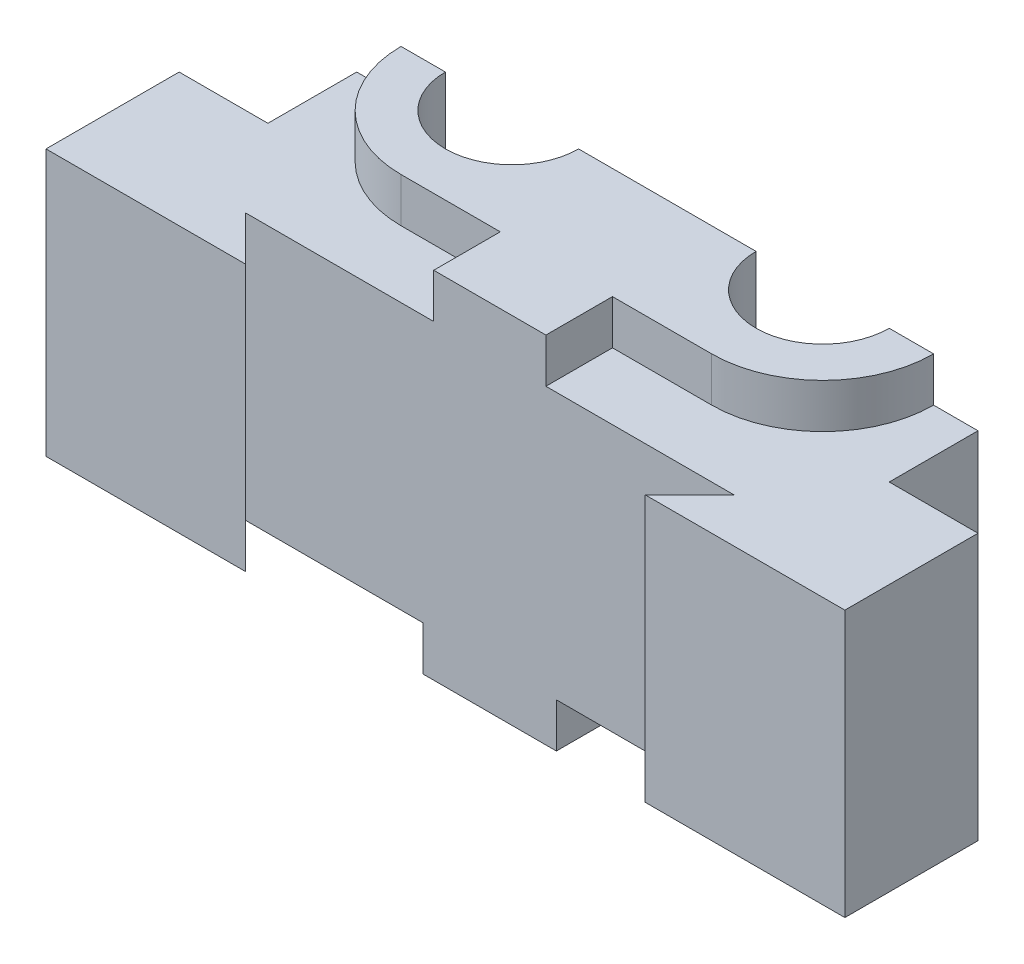
SolidWorks part; units mm, degrees
ref_plane "Front Plane" through (0, 0, 0) normal (0, 0, 1) x (1, 0, 0)
ref_plane "Top Plane" through (0, 0, 0) normal (0, 1, 0) x (1, 0, 0)
ref_plane "Right Plane" through (0, 0, 0) normal (1, 0, 0) x (0, 0, -1)
sketch "Sketch1" plane through (0, 0, 0) normal (0, 1, 0) x (1, 0, 0)
  line L0 (0, 59.4374) -> (0, -59.4374) construction
  line L1 (-91.3835, 0) -> (103.8781, 0) construction
  line L2 (-35, 0) -> (35, 0)
  line L3 (-35, 0) -> (-35, -10)
  line L4 (35, 0) -> (35, -10)
  line L5 (-45, -25) -> (-22.5, -25)
  line L6 (-45, -25) -> (-45, -10)
  line L7 (-45, -10) -> (-35, -10)
  line L8 (45, -10) -> (35, -10)
  line L9 (45, -25) -> (45, -10)
  line L10 (-27.5, -20) -> (27.5, -20)
  line L11 (-27.5, -20) -> (-22.5, -25)
  line L12 (27.5, -20) -> (22.5, -25)
  line L13 (22.5, -25) -> (45, -25)
  point P7 (0, 0)
  point P17 (0, -20)
  dimension "D1" = 70
  dimension "D2" = 10
  dimension "D3" = 15
  dimension "D4" = 90
  dimension "D5" = 55
  dimension "D6" = 5
  dimension "D7" = 45
  dimension "D8" = 22.5
extrude "Boss-Extrude1" add sketch "Sketch1" along normal blind 30
sketch "Sketch3" plane through (0, 30, 0) normal (0, 1, 0) x (1, 0, 0)
  line L0 (35, 0) -> (-35, 0) construction
  line L1 (0, 23.9193) -> (0, -33.7486) construction
  line L3 (-6.3201, -20) -> (6.3201, -20)
  line L4 (-27.5, -20) -> (27.5, -20) construction
  line L5 (-6.3201, -20) -> (-6.3201, -12.5)
  line L6 (-6.3201, -12.5) -> (-17.5, -12.5)
  line L7 (6.3201, -20) -> (6.3201, -12.5)
  line L8 (6.3201, -12.5) -> (17.5, -12.5)
  line L9 (-35, 0) -> (35, 0) construction
  line L10 (-30, 0) -> (30, 0)
  arc A0 (-25, 0) -> (-10, 0) centre (-17.5, 0) ccw
  arc A1 (10, 0) -> (25, 0) centre (17.5, 0) ccw
  arc A2 (-30, 0) -> (-17.5, -12.5) centre (-17.5, 0) ccw
  arc A3 (30, 0) -> (17.5, -12.5) centre (17.5, 0) cw
  point P15 (0, -20)
  line M15 (-27.5, -20) -> (27.5, -20)
  line M21 (35, 0) -> (-35, 0)
  dimension "D1" = 12.5
  dimension "D2" = 7.5
  dimension "D5" = 7.5
  dimension "D3" = 12.6403
  dimension "D4" = 17.5
extrude "Boss-Extrude2" add sketch "Sketch3" along normal blind 5 contours A3 A1 A0 A2 L6 L5 L7 L8 M21 M15 region at (0, 30, 8.3432)
sketch "Sketch5" plane through (0, 0, 0) normal (0, -1, 0) x (1, 0, 0)
  line L0 (0, 42.5009) -> (0, -21.0991) construction
  line L1 (-7.5, 20) -> (7.5, 20)
  line L2 (-27.5, 20) -> (27.5, 20) construction
  line L3 (35, 0) -> (-35, 0) construction
  line L4 (-30, 0) -> (30, 0) construction
  line L5 (-17.5, 12.5) -> (-7.5, 12.5)
  line L6 (-7.5, 12.5) -> (-7.5, 20)
  line L7 (7.5, 12.5) -> (7.5, 20)
  line L8 (17.5, 12.5) -> (7.5, 12.5)
  line L9 (-30, 0) -> (30, 0)
  arc A0 (-17.5, 12.5) -> (-30, 0) centre (-17.5, 0) ccw
  arc A1 (-10, 0) -> (-25, 0) centre (-17.5, 0) ccw
  arc A2 (10, 0) -> (25, 0) centre (17.5, 0) cw
  arc A3 (17.5, 12.5) -> (30, 0) centre (17.5, 0) cw
  point P7 (0, 20)
  line M14 (-35, 0) -> (35, 0)
  line M20 (27.5, 20) -> (-27.5, 20)
  dimension "D2" = 25
  dimension "D3" = 15
  dimension "D1" = 15
  dimension "D4" = 17.5
extrude "Boss-Extrude3" add sketch "Sketch5" along normal blind 5 contours A3 L8 L7 L6 L5 A0 A1 A2 M20 M14 region at (0, 0, 8.5694)
extrude "Cut-Extrude1" cut sketch "Sketch5<3>" against normal through all contours L9 A1 region at (-17.5, 0, 3.1831)
sketch "Sketch5<3>" plane through (0, 0, 0) normal (0, -1, 0) x (1, 0, 0) same geometry as "Sketch5"
extrude "Cut-Extrude2" cut sketch "Sketch3<3>" against normal through all contours L10 A1 region at (17.5, 30, 3.1831)
sketch "Sketch3<3>" plane through (0, 30, 0) normal (0, 1, 0) x (1, 0, 0) same geometry as "Sketch3"
sketch "Sketch7" plane through (0, 0, 0) normal (0, 0, -1) x (-1, 0, 0)
  line L0 (0, 51.1649) -> (0, -15.0379) construction
  line L1 (-35, 30) -> (-30, 30) construction
  circle A0 centre (0, 0) radius 2.25
  circle A1 centre (0, 30) radius 2.25
  circle A2 centre (-30, 22.5) radius 2.25
  circle A3 centre (-30, 7.5) radius 2.25
  circle A6 centre (30, 7.5) radius 2.25
  circle A7 centre (30, 22.5) radius 2.25
  dimension "D1" = 4.5
  dimension "D2" = 15
  dimension "D3" = 7.5
  dimension "D4" = 30
  dimension "D5" = 30
  dimension "D6" = 30
extrude "Cut-Extrude3" cut sketch "Sketch7" against normal blind 15
